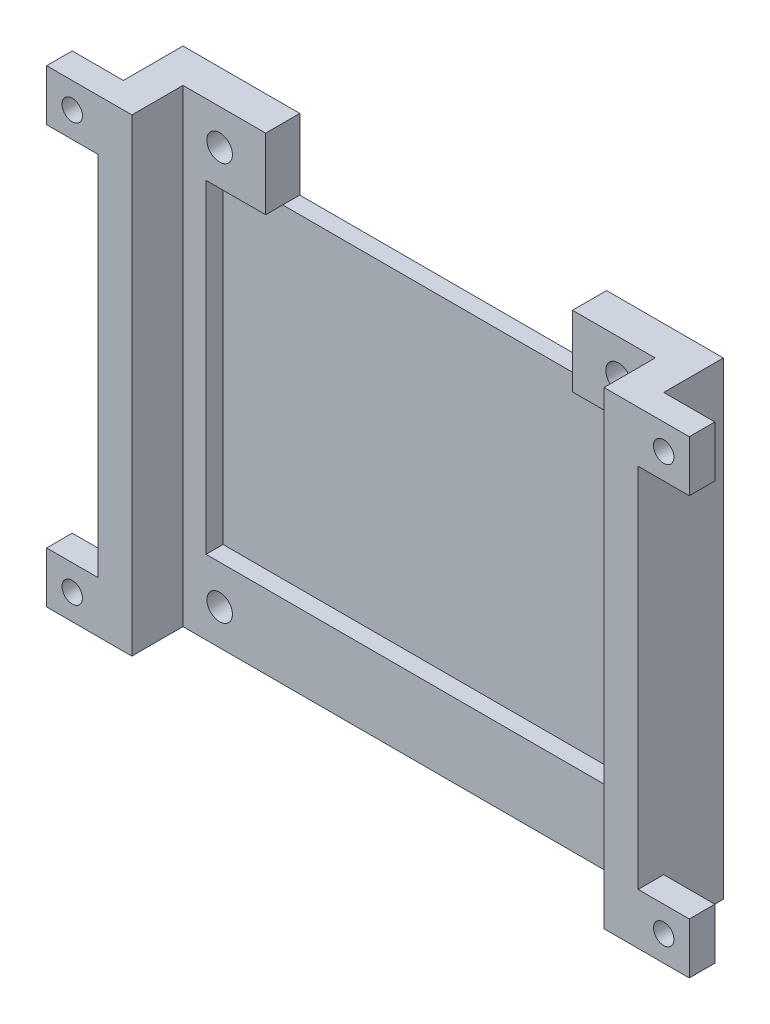
SolidWorks part; units mm, degrees
ref_plane "前视基准面" through (0, 0, 0) normal (0, 0, 1) x (1, 0, 0)
ref_plane "上视基准面" through (0, 0, 0) normal (0, 1, 0) x (1, 0, 0)
ref_plane "右视基准面" through (0, 0, 0) normal (1, 0, 0) x (0, 0, -1)
other "Configuration Table"
sketch "草图1" plane through (0, 0, 0) normal (0, 0, 1) x (1, 0, 0)
  line L9 (-13.85, 13.75) -> (13.85, 13.75)
  line L10 (-13.85, 13.75) -> (-13.85, -13.75)
  line L11 (-13.85, -13.75) -> (13.85, -13.75)
  line L12 (13.85, 13.75) -> (13.85, -13.75)
  line L13 (-13.85, 13.75) -> (-15.85, 13.75)
  line L14 (-13.85, 13.75) -> (-13.85, -13.75)
  line L15 (-13.85, -13.75) -> (-15.85, -13.75)
  line L16 (-15.85, 13.75) -> (-15.85, -13.75)
  line L17 (13.85, -13.75) -> (15.85, -13.75)
  line L18 (13.85, -13.75) -> (13.85, 13.75)
  line L19 (13.85, 13.75) -> (15.85, 13.75)
  line L20 (15.85, -13.75) -> (15.85, 13.75)
  line L21 (-15.85, 13.75) -> (-18.85, 13.75)
  line L42 (-15.85, 13.75) -> (-15.85, 10.75)
  line L43 (-15.85, 10.75) -> (-18.85, 10.75)
  line L44 (-18.85, 13.75) -> (-18.85, 10.75)
  line L45 (-15.85, -13.75) -> (-18.85, -13.75)
  line L46 (-15.85, -13.75) -> (-15.85, -10.75)
  line L47 (-15.85, -10.75) -> (-18.85, -10.75)
  line L48 (-18.85, -13.75) -> (-18.85, -10.75)
  line L49 (15.85, -13.75) -> (18.85, -13.75)
  line L50 (15.85, -13.75) -> (15.85, -10.75)
  line L51 (15.85, -10.75) -> (18.85, -10.75)
  line L52 (18.85, -13.75) -> (18.85, -10.75)
  line L53 (15.85, 13.75) -> (18.85, 13.75)
  line L54 (15.85, 13.75) -> (15.85, 10.75)
  line L55 (15.85, 10.75) -> (18.85, 10.75)
  line L56 (18.85, 13.75) -> (18.85, 10.75)
  circle A12 centre (-17.35, 12.25) radius 0.6
  circle A13 centre (-17.35, -12.25) radius 0.6
  circle A14 centre (17.35, -12.25) radius 0.6
  circle A15 centre (17.35, 12.25) radius 0.6
  point P4 (0, 13.75)
  point P6 (-13.85, 0)
  point P31 (0, 0)
  point P32 (-17.35, 13.75)
  point P33 (-18.85, 12.25)
  point P34 (0, 0)
  point P35 (18.85, -12.25)
  point P36 (0, 0)
  point P37 (17.35, -13.75)
  point P38 (0, 0)
  point P39 (0, 0)
  point P40 (0, 0)
  point P41 (0, 0)
  dimension "D4" = 3
  dimension "D1" = 27.5
  dimension "D2" = 27.7
  dimension "D3" = 2
  dimension "D6" = 1.2
  dimension "D5" = 3
extrude "凸台-拉伸1" add sketch "草图1" along normal blind 2 contours L11 L12 L9 L10
extrude "凸台-拉伸2" add sketch "草图1<13>" along normal blind 5 contours L13 L16 L15 L10 | L17 L20 L19 L12 region at (-14.85, 0, 0) region at (14.85, 0, 0)
sketch "草图1<13>" plane through (0, 0, 0) normal (0, 0, 1) x (1, 0, 0) same geometry as "草图1"
sketch "草图2" plane through (0, 0, 2) normal (0, 0, 1) x (1, 0, 0)
  line L1 (-9, 9.6) -> (9, 9.6)
  line L2 (-9, 9.6) -> (-9, 13.75)
  line L3 (-9, 13.75) -> (9, 13.75)
  line L4 (9, 9.6) -> (9, 13.75)
  line L5 (-13.85, 13.75) -> (13.85, 13.75) construction
  line L7 (-12.5, 9.6) -> (12.5, 9.6)
  line L8 (-12.5, 9.6) -> (-12.5, -9.4)
  line L9 (-12.5, -9.4) -> (12.5, -9.4)
  line L10 (12.5, 9.6) -> (12.5, -9.4)
  circle A0 centre (-11.7, 11.675) radius 0.75
  circle A1 centre (11.7, 11.675) radius 0.75
  circle A2 centre (-11.7, -11.675) radius 0.75
  circle A3 centre (11.7, -11.675) radius 0.75
  point P4 (0, 13.75)
  point P16 (0, 0)
  point P24 (0, 0)
  point P25 (0, 0)
  point P26 (0, 0)
  point P27 (0, 0)
  point P28 (0, 0)
  point P29 (0, 0)
  point P30 (0, -9.4)
  point P31 (0, 0)
  dimension "D3" = 1.5
  dimension "D1" = 4.15
  dimension "D2" = 18
  dimension "D4" = 25
  dimension "D5" = 19
extrude "切除-拉伸1" cut sketch "草图2" against normal through all contours A0 | L2 L3 L4 L1 | A1 | A3 | A2
extrude "切除-拉伸2" cut sketch "草图2<3>" against normal blind 1 contours L9 L10 L7 L8
sketch "草图2<3>" plane through (0, 0, 2) normal (0, 0, 1) x (1, 0, 0) same geometry as "草图2"
extrude "凸台-拉伸3" add sketch "草图1<14>" against normal blind 1.5 from surface contours L21 L44 L43 L16 A12 | L48 L45 L16 L47 A13 | L49 L52 L51 L20 A14 | L56 L53 L20 L55 A15 region at (-15.8924, 12.25, 0) region at (17.35, 13.7076, 0) region at (-17.35, -13.7076, 0) region at (15.8924, -12.25, 0) starting at face at (14.85, 0, 5)
sketch "草图1<14>" plane through (0, 0, 0) normal (0, 0, 1) x (1, 0, 0) same geometry as "草图1"
